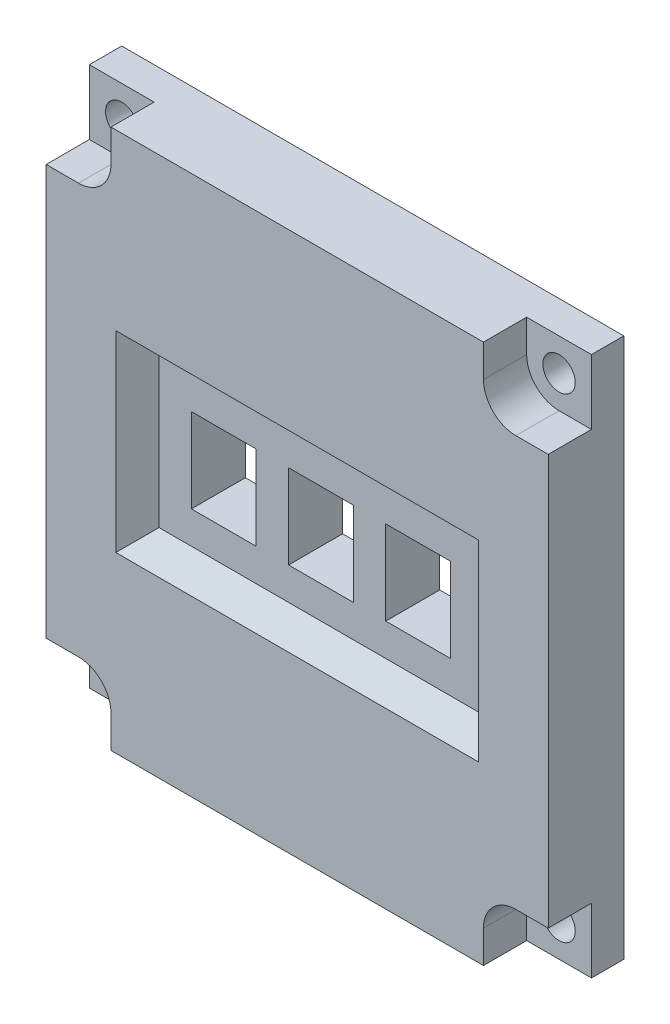
SolidWorks part; units mm, degrees
ref_plane "Front Plane" through (0, 0, 0) normal (0, 0, 1) x (1, 0, 0)
ref_plane "Top Plane" through (0, 0, 0) normal (0, 1, 0) x (1, 0, 0)
ref_plane "Right Plane" through (0, 0, 0) normal (1, 0, 0) x (0, 0, -1)
sketch "Sketch1" plane through (0, 0, 0) normal (0, 0, 1) x (1, 0, 0)
  line L1 (-23.25, 25) -> (23.25, 25)
  line L2 (-23.25, 25) -> (-23.25, -25)
  line L3 (-23.25, -25) -> (23.25, -25)
  line L4 (23.25, 25) -> (23.25, -25)
  dimension "D1" = 46.5
  dimension "D2" = 50
  dimension "D3" = 25
  dimension "D4" = 23.25
extrude "Boss-Extrude1" add sketch "Sketch1" along normal blind 7
sketch "Sketch2" plane through (0, 0, 7) normal (0, 0, 1) x (1, 0, 0)
  line L0 (-23.25, 25) -> (-23.25, -25) construction
  line L1 (-16.8, 8.9) -> (16.8, 8.9)
  line L2 (-16.8, 8.9) -> (-16.8, -8.9)
  line L3 (-16.8, -8.9) -> (16.8, -8.9)
  line L4 (16.8, 8.9) -> (16.8, -8.9)
  dimension "D1" = 33.6
  dimension "D2" = 6.45
  dimension "D3" = 8.9
  dimension "D4" = 17.8
extrude "Cut-Extrude1" cut sketch "Sketch2" against normal blind 2
chamfer "Chamfer1" distance 2 angle 45 4 edges at (0, -8.9, 5) (16.8, 0, 5) (0, 8.9, 5) (-16.8, 0, 5)
sketch "Sketch3" plane through (0, 0, 7) normal (0, 0, 1) x (1, 0, 0)
  line L0 (-33.1361, 0) -> (46.0913, 0) construction
  line L1 (23.25, -25) -> (17.25, -25)
  line L2 (23.25, -25) -> (23.25, -19)
  line L3 (23.25, -19) -> (20.25, -19)
  line L4 (17.25, -25) -> (17.25, -22)
  line L5 (-23.25, -25) -> (-17.25, -25)
  line L6 (-23.25, -25) -> (-23.25, -19)
  line L7 (-23.25, -19) -> (-20.25, -19)
  line L8 (-17.25, -25) -> (-17.25, -22)
  line L9 (-17.25, 25) -> (-17.25, 22)
  line L10 (-23.25, 19) -> (-20.25, 19)
  line L11 (-23.25, 25) -> (-23.25, 19)
  line L12 (-23.25, 25) -> (-17.25, 25)
  line L13 (17.25, 25) -> (17.25, 22)
  line L14 (23.25, 19) -> (20.25, 19)
  line L15 (23.25, 25) -> (23.25, 19)
  line L16 (23.25, 25) -> (17.25, 25)
  arc A1 (20.25, -19) -> (17.25, -22) centre (20.25, -22) ccw
  arc A2 (-17.25, -22) -> (-20.25, -19) centre (-20.25, -22) ccw
  arc A3 (-17.25, 22) -> (-20.25, 19) centre (-20.25, 22) cw
  arc A4 (20.25, 19) -> (17.25, 22) centre (20.25, 22) cw
  point P15 (-17.25, -19)
  point P31 (-17.25, 19)
  dimension "D1" = 3
  dimension "D5" = 3
  dimension "D2" = 3
  dimension "D3" = 3
  dimension "D4" = 3
  dimension "D6" = 3
extrude "Cut-Extrude2" cut sketch "Sketch3" against normal blind 4
sketch "Sketch4" plane through (0, 0, 7) normal (0, 0, 1) x (1, 0, 0)
  line L0 (-23.25, 25) -> (-23.25, 19) construction
  line L1 (-17.25, 25) -> (-23.25, 25) construction
  line L2 (20.25, 19) -> (23.25, 19) construction
  line L4 (23.25, 19) -> (23.25, 25) construction
  line L5 (-32.0664, 0) -> (36.204, 0) construction
  circle A0 centre (-20.25, 22) radius 1.5
  circle A1 centre (20.25, 22) radius 1.5
  circle A2 centre (20.25, -22) radius 1.5
  circle A3 centre (-20.25, -22) radius 1.5
  dimension "D3" = 3
  dimension "D4" = 3
  dimension "D1" = 3
  dimension "D2" = 3
  dimension "D5" = 3
  dimension "D6" = 3
extrude "Cut-Extrude3" cut sketch "Sketch4" against normal blind 10
sketch "Sketch5" plane through (0, 0, 5) normal (0, 0, 1) x (1, 0, 0)
  line L0 (-14.8, 6.9) -> (-14.8, -6.9) construction
  line L1 (-11.8, 3.9) -> (-5.8, 3.9)
  line L2 (-11.8, 3.9) -> (-11.8, -3.9)
  line L3 (-11.8, -3.9) -> (-5.8, -3.9)
  line L4 (-5.8, 3.9) -> (-5.8, -3.9)
  line L5 (-2.8, 3.9) -> (3.2, 3.9)
  line L6 (-2.8, 3.9) -> (-2.8, -3.9)
  line L7 (-2.8, -3.9) -> (3.2, -3.9)
  line L8 (3.2, 3.9) -> (3.2, -3.9)
  line L9 (6.2, 3.9) -> (12.2, 3.9)
  line L10 (6.2, 3.9) -> (6.2, -3.9)
  line L11 (6.2, -3.9) -> (12.2, -3.9)
  line L12 (12.2, 3.9) -> (12.2, -3.9)
  line L13 (14.8, 6.9) -> (-14.8, 6.9) construction
  line L14 (-14.8, -6.9) -> (14.8, -6.9) construction
  dimension "D1" = 6
  dimension "D2" = 3
  dimension "D3" = 3
  dimension "D4" = 3
  dimension "D5" = 6
  dimension "D6" = 6
  dimension "D7" = 3
  dimension "D8" = 3
  dimension "D9" = 3
  dimension "D10" = 0
  dimension "D11" = 0
  dimension "D12" = 0
extrude "Cut-Extrude4" cut sketch "Sketch5" against normal blind 10
